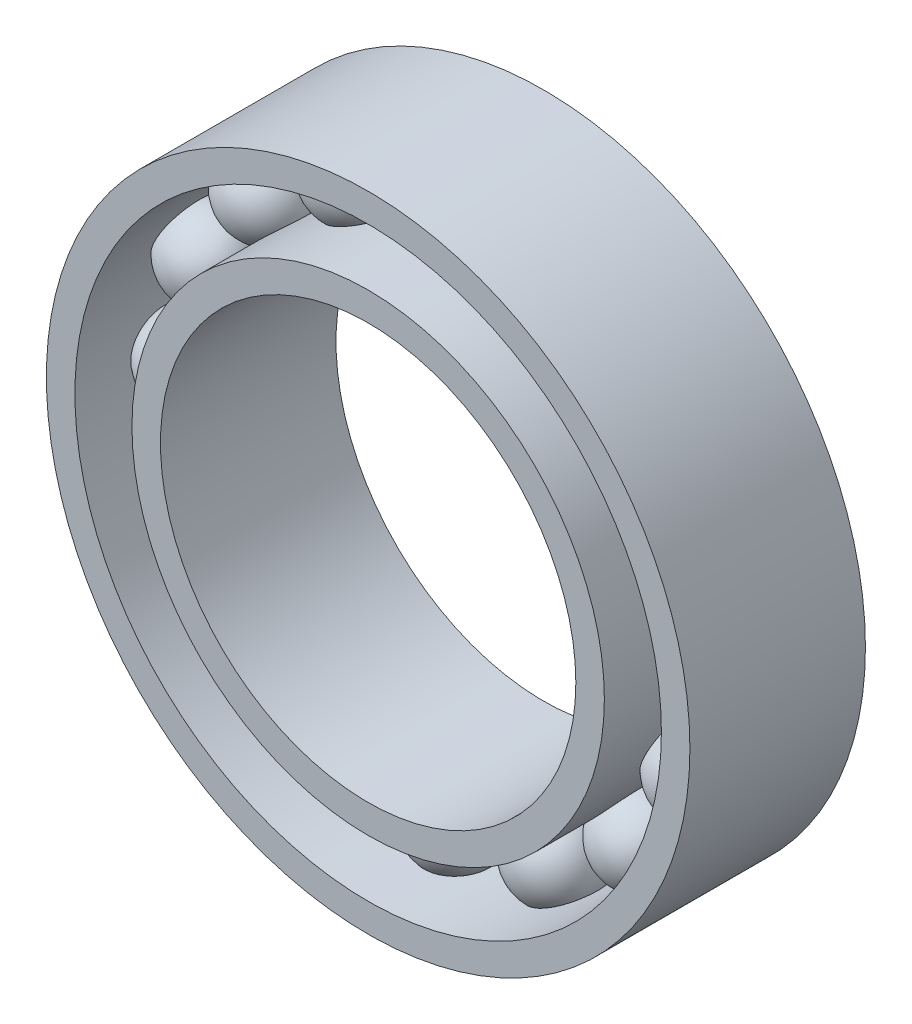
SolidWorks part; units mm, degrees
ref_plane "Front Plane" through (0, 0, 0) normal (0, 0, 1) x (1, 0, 0)
ref_plane "Top Plane" through (0, 0, 0) normal (0, 1, 0) x (1, 0, 0)
ref_plane "Right Plane" through (0, 0, 0) normal (1, 0, 0) x (0, 0, -1)
sketch "Sketch1" plane through (0, 0, 0) normal (0, 0, 1) x (1, 0, 0)
  line L0 (0, 0) -> (3.55, 0) construction
  line L1 (3.55, 0) -> (5.5, 0) construction
  line L2 (0, 0) -> (0, 3.55) construction
  line L3 (0, 3.55) -> (0, 4.525) construction
  line L4 (0, 4.525) -> (0, 5.5) construction
  circle A0 centre (0, 0) radius 5.5
  circle A1 centre (0, 0) radius 3.55
  circle A2 centre (0, 0) radius 4.0375 construction
  circle A3 centre (0, 0) radius 5.0125 construction
  circle A4 centre (0, 0) radius 4.525 construction
  point P7 (4.525, 0)
  point P13 (0, 5.0125)
  point P14 (0, 4.0375)
  dimension "D1" = 7.1
  dimension "D2" = 11
extrude "Boss-Extrude1" add sketch "Sketch1" along normal blind 3
sketch "Sketch2" plane through (0, 0, 0) normal (0, 0, 1) x (1, 0, 0)
  circle A0 centre (0, 0) radius 4.0375
  circle A1 centre (0, 0) radius 5.0125
  circle A2 centre (0, 0) radius 4.0375 construction
  circle A3 centre (0, 0) radius 5.0125 construction
extrude "Cut-Extrude1" cut sketch "Sketch2" along normal up to next
sketch "Sketch3" plane through (0, 0, 0) normal (1, 0, 0) x (0, 0, -1)
  line L1 (0, 4.525) -> (-3, 4.525) construction
  line L2 (0, 3.55) -> (0, 4.525) construction
  line L3 (-3, 5.5) -> (-3, -5.5) construction
  line L4 (-1.5, 5.2562) -> (-1.5, 3.7937)
  line L5 (-1.5, 3.55) -> (-1.5, 4.0375) construction
  line L6 (0, 3.55) -> (-3, 3.55) construction
  line L7 (0, 4.0375) -> (-3, 4.0375) construction
  arc A0 (-1.5, 3.7937) -> (-1.5, 5.2562) centre (-1.5, 4.525) ccw
  point P9 (-1.5, 4.525)
  point P11 (-1.5, 4.525)
  point P18 (-1.5, 3.7937)
revolve "Revolve1" add sketch "Sketch3" angle 360 about L4
ref_axis "Axis1" through (0, 0, -0.2) along (0, 0, 1)
pattern_circular "CirPattern1" count 16 over 360 about axis through (0, 0, -0.2) along (0, 0, 1) of "Revolve1"
